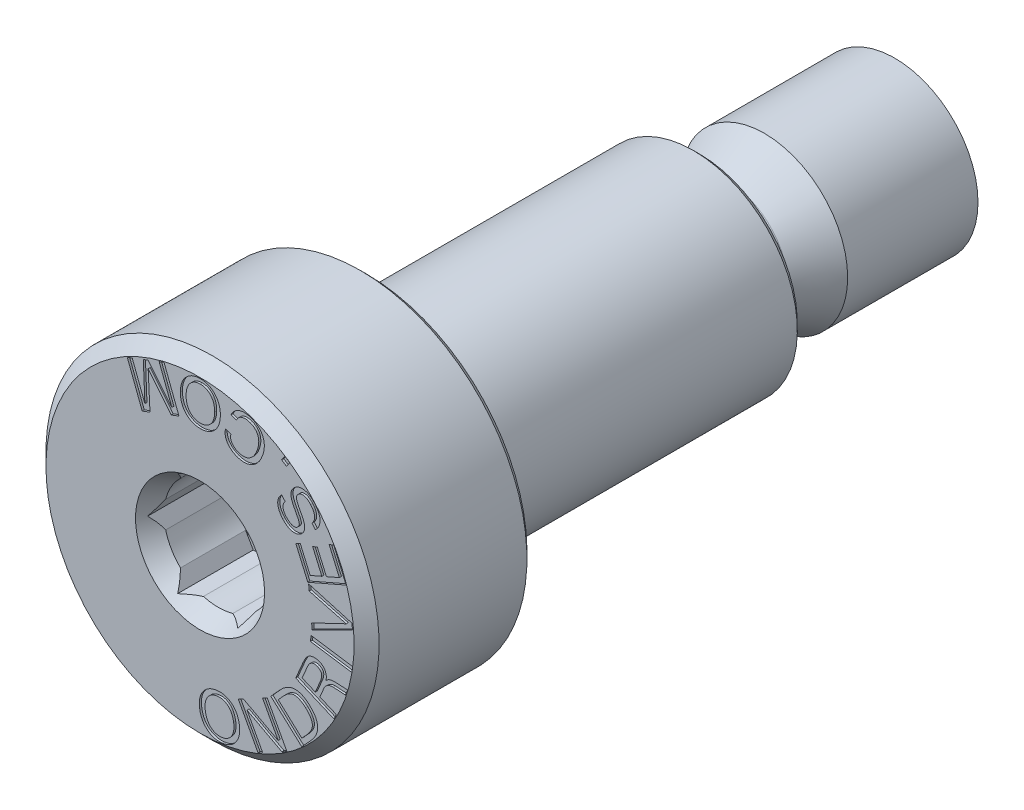
SolidWorks part; units mm, degrees
material "AISI 303 STAINLESS STEEL"
ref_plane "Body Centre" through (0, 0, 0) normal (0, 0, 1) x (1, 0, 0)
ref_plane "Horizontal Centre" through (0, 0, 0) normal (0, 1, 0) x (1, 0, 0)
ref_plane "Vertical Centre" through (0, 0, 0) normal (1, 0, 0) x (0, 0, -1)
other "Configuration Table"
sketch "Sketch1" plane through (0, 0, 0) normal (1, 0, 0) x (0, 0, -1)
  line L0 (0, 2.4935) -> (0, 4)
  line L1 (0, 4) -> (-4, 4)
  line L2 (-4, 4) -> (-4, 0)
  line L3 (-4, 0) -> (13, 0)
  line L4 (13, 0) -> (13, 2)
  line L5 (13, 2) -> (8, 2)
  line L6 (8, 2) -> (8, 2.4935)
  line L7 (8, 2.4935) -> (0, 2.4935)
  line L8 (-4, 0) -> (-8, 0) construction
  dimension "HEAD_DIA" = 8
  dimension "HEAD_HEIGHT" = 4
  dimension "SHOULDER_DIA" = 4.987
  dimension "SHOULDER_LENGTH" = 8
  dimension "THREAD" = 4
  dimension "THREAD_LENGTH" = 5
revolve "BODY" add sketch "Sketch1" angle 360 about L8
sketch "Sketch2" plane through (0, 0, 0) normal (1, 0, 0) x (0, 0, -1)
  line L0 (-4, 0) -> (-0.8195, 0)
  line L1 (-4, 4) -> (-4, -4) construction
  line L2 (-0.8195, 0) -> (-1.6, 1.299)
  line L3 (-1.6, 1.299) -> (-3.5653, 1.299)
  line L4 (-3.5653, 1.299) -> (-4, 1.55)
  line L5 (-4, 1.55) -> (-4, 0)
  line L6 (-0.8195, 0) -> (2.361, 0) construction
  dimension "HEX_DRILL" = 2.598
  dimension "HEX_CHAMFER_ANGLE" = 30
  dimension "HEX_DRILL_DEPTH" = 2.4
  dimension "DRILL_ANGLE" = 59
  dimension "HEX_CHAMFER_DIA" = 3.1
revolve "HEX DRILL" cut sketch "Sketch2" angle 360 about L6
sketch "Sketch3" plane through (0, 0, 4) normal (0, 0, 1) x (1, 0, 0)
  line L1 (0.7217, 1.25) -> (-0.7217, 1.25)
  line L2 (-0.7217, 1.25) -> (-1.4434, 0)
  line L3 (-1.4434, 0) -> (-0.7217, -1.25)
  line L4 (-0.7217, -1.25) -> (0.7217, -1.25)
  line L5 (0.7217, -1.25) -> (1.4434, 0)
  line L6 (1.4434, 0) -> (0.7217, 1.25)
  circle A0 centre (0, 0) radius 1.25 construction
  dimension "HEX" = 2.5
extrude "HEX" cut sketch "Sketch3" against normal blind 2
chamfer "SHOULDER CHAMFER" distance 0.15 angle 45 1 edges at (0, 2.4935, -8)
chamfer "HEAD CHAMFER" distance 0.3 angle 45 1 edges at (0, 4, 4)
chamfer "HEAD UNDERSIDE CHAMFER" distance 0.15 angle 45 1 edges at (0, 4, 0)
sketch "Sketch4" plane through (0, 0, 0) normal (1, 0, 0) x (0, 0, -1)
  line L0 (0, -4) -> (0, 4) construction
  line L1 (0.2, 2.21) -> (0.6, 2.21)
  line L2 (0.6, 2.21) -> (0.8835, 2.4935)
  line L3 (7.85, 2.4935) -> (0, 2.4935) construction
  line L4 (0.8835, 2.4935) -> (0.0183, 2.4935)
  line L5 (0, 0) -> (0.8652, 0) construction
  line L6 (-0.0611, 3.02) -> (0.0611, 3.02) construction
  line L7 (0, -3.85) -> (0, 3.85) construction
  arc A0 (0.0183, 2.4935) -> (0.2, 2.21) centre (0.2, 2.41) ccw
  arc A1 (0, 3.5) -> (1.29, 2.21) centre (1.29, 3.5) ccw construction
  circle A2 centre (0.5172, 2.41) radius 0.2 construction
  arc A3 (0, 3.5) -> (0.25, 3.25) centre (0.25, 3.5) ccw construction
  circle A4 centre (0.2, 3.02) radius 0.2 construction
  point P26 (0, 3.02)
  dimension "D2" = 1.29
  dimension "HEAD_UCUT_RAD" = 0.2
  dimension "D3" = 0.2
  dimension "D4" = 0.25
  dimension "D7" = 0.4
  dimension "D1" = 7
  dimension "HEAD_UCUT_ANGLE" = 45
  dimension "HEAD_UCUT_DIA" = 4.42
  dimension "HEAD_UCUT_LENGTH" = 0.6
  dimension "D5" = 0.2835
  dimension "D6" = 6.5
  dimension "D8" = 5.64
  dimension "D9" = 6.04
revolve "Cut-Revolve2" cut sketch "Sketch4" angle 360 about L5
fillet "Fillet1" radius 0.2 1 edges at (2.21, 0, -0.6)
sketch "Sketch5" plane through (0, 0, 0) normal (1, 0, 0) x (0, 0, -1)
  line L0 (0, 0) -> (0.8652, 0) construction
  line L1 (0, 0) -> (0.8652, 0) construction
  line L2 (0.0183, 2.4935) -> (0, 2.4935)
  line L3 (0, 2.4935) -> (0, 2.41)
  arc A0 (0, 2.41) -> (0.0183, 2.4935) centre (0.2, 2.41) ccw
  arc A1 (0.0183, 2.4935) -> (0.2, 2.21) centre (0.2, 2.41) ccw construction
revolve "Cut-Revolve4" cut sketch "Sketch5" angle 360 about L1
sketch "Sketch6" plane through (0, 0, 0) normal (1, 0, 0) x (0, 0, -1)
  line L0 (8, -2.3435) -> (8, 2.3435) construction
  line L1 (8.4, 1.45) -> (8.6, 1.45)
  line L2 (8.6, 1.45) -> (9.5526, 2)
  line L3 (8.8771, 1.61) -> (6.8924, 1.61) construction
  line L4 (9.5526, 2) -> (8, 2)
  line L5 (0, 0) -> (1.5526, 0) construction
  line L6 (8, 2) -> (8, 1.85)
  line L7 (8, -2) -> (8, 2) construction
  line L8 (13, 2) -> (13, 1.45)
  line L9 (13, -2) -> (13, 2) construction
  line L10 (13, 1.45) -> (12.6825, 2)
  line L11 (12.6825, 2) -> (13, 2)
  line L12 (13, 2) -> (8, 2) construction
  arc A0 (8.4, 1.45) -> (8, 1.85) centre (8.4, 1.85) cw
  arc A1 (8, 2) -> (8.55, 1.45) centre (8.55, 2) ccw construction
  dimension "D2" = 1.5526
  dimension "THREAD_UCUT_RAD" = 0.4
  dimension "D5" = 0.55
  dimension "D3" = 1.61
  dimension "D1" = 30
  dimension "THREAD_UCUT_ANGLE" = 30
  dimension "THREAD_UCUT_DIA" = 2.9
  dimension "D4" = 0.55
  dimension "D6" = 0.8771
  dimension "THREAD_UCUT_LENGTH" = 0.6
revolve "Cut-Revolve3" cut sketch "Sketch6" angle 360 about L5
fillet "Fillet2" radius 0.2 1 edges at (1.45, 0, -8.6)
sketch "Sketch7" plane through (0, 0, 4) normal (0, 0, 1) x (1, 0, 0)
  text T0 "ONDRIVES.COM" font "Microsoft Sans Serif" height 1
extrude "Cut-Extrude1" cut sketch "Sketch7" against normal blind 0.05
